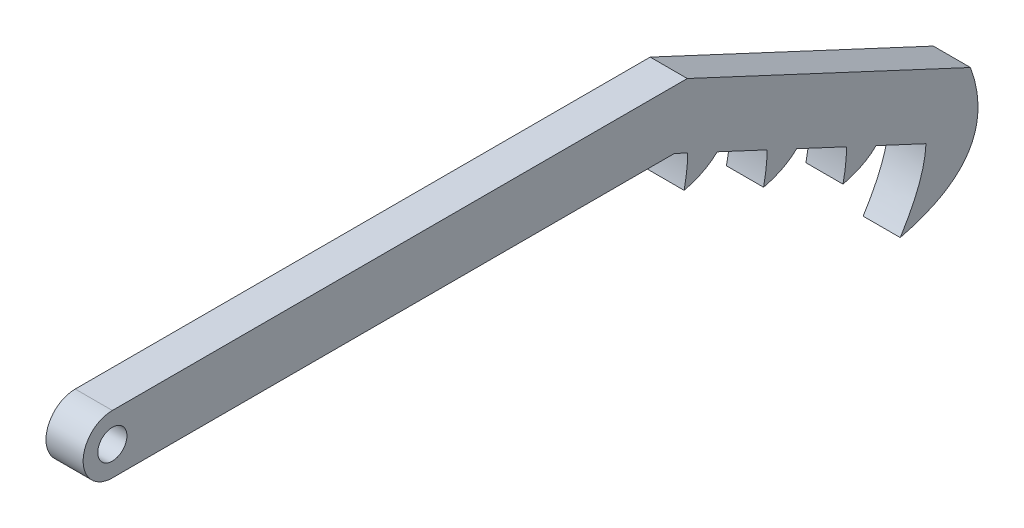
SolidWorks part; units mm, degrees
ref_plane "Front Plane" through (0, 0, 0) normal (0, 0, 1) x (1, 0, 0)
ref_plane "Top Plane" through (0, 0, 0) normal (0, 1, 0) x (1, 0, 0)
ref_plane "Right Plane" through (0, 0, 0) normal (1, 0, 0) x (0, 0, -1)
sketch "Sketch1" plane through (0, 0, 0) normal (1, 0, 0) x (0, 0, -1)
  line L0 (-57.9219, 44.5435) -> (-40.0493, 54.8622)
  line L1 (-40.0493, 49.8622) -> (56.1047, 49.8622)
  line L2 (56.1047, 49.8622) -> (102.5472, 28.2057)
  line L3 (-40.0493, 59.8622) -> (58.3217, 59.8622)
  line L4 (58.3217, 59.8622) -> (106.7734, 37.2688)
  line L5 (56.1047, 49.8622) -> (84.5622, 36.5923) construction
  line L6 (58.3217, 59.8622) -> (88.7883, 45.6554) construction
  line L7 (102.5472, 28.2057) -> (106.7734, 37.2688)
  line L8 (102.5472, 28.2057) -> (111.6103, 23.9795)
  line L9 (93.4842, 32.4319) -> (106.7734, 37.2688)
  circle A0 centre (-57.9219, 44.5435) radius 15.875
  circle A1 centre (-40.0493, 54.8622) radius 4.7625
  circle A2 centre (-40.0493, 54.8622) radius 2.5
  circle A3 centre (-40.0493, 54.8622) radius 5
  parabola Q0 (106.7734, 37.2688) -> (94.7552, 18.0752) focus (102.5472, 28.2057) apex (107.0788, 26.0926)
  parabola Q1 (99.1632, 29.7837) -> (94.7552, 18.0752) focus (93.4842, 32.4319) apex (98.5101, 34.2612)
  parabola Q2 (93.4202, 43.4955) -> (84.9631, 30.8885) focus (87.9414, 37.2725) apex (91.341, 34.5621)
  parabola Q3 (85.5686, 36.123) -> (84.9631, 30.8885) focus (78.3442, 40.2408) apex (83.762, 43.3694)
  parabola Q4 (79.8256, 49.8348) -> (71.3685, 37.2277) focus (74.3468, 43.6117) apex (77.7464, 40.9013)
  parabola Q5 (71.974, 42.4623) -> (71.3685, 37.2277) focus (64.7496, 46.58) apex (70.1674, 49.7086)
  parabola Q6 (66.2309, 56.1741) -> (57.7739, 43.567) focus (60.7522, 49.951) apex (64.1518, 47.2406)
  parabola Q7 (58.3794, 48.8015) -> (57.7739, 43.567) focus (51.155, 52.9193) apex (56.5728, 56.0479)
  point P12 (93.4842, 32.4319)
  point P19 (100.1288, 34.8504)
  point P30 (0, 0)
  dimension "D1" = 10
  dimension "D2" = 12.4745
  dimension "D3" = 5
  dimension "D4" = 15
extrude "Boss-Extrude1" add sketch "Sketch1" along normal blind 6.35 contours A2 A1 | A3 A0 A1 | L0 A3 A0 | A0 A3 L0 | Q6 L4 L3 A3 L1 L2 | L4 Q6 L2 Q4 | L4 Q4 L2 Q2 | L4 Q2 L2 L9 | L9 L2 L7 | Q0 L7 L8 | L2 Q1 Q0 L8 | L2 Q3 Q2 | L2 Q5 Q4 | L2 Q7 Q6 | A2 region at (0, 52.862, 44.5166) region at (0, 51.9936, 44.0152) region at (0, 53.0598, 44.5079) region at (0, 59.3323, 41.2471) region at (0, 54.7102, -15.0994) region at (0, 47.8087, -72.3396) region at (0, 46.1053, -60.0268) region at (0, 41.4694, -85.9342) region at (0, 37.45, -97.3772) region at (0, 39.7661, -73.6214) region at (0, 30.7591, -105.9447) region at (0, 32.6355, -100.9349) region at (0, 33.4268, -87.216) region at (0, 23.9786, -100.9688)
sketch "Sketch2" plane through (6.35, 0, 0) normal (1, 0, 0) x (0, 0, -1)
  arc A0 (-40.0493, 59.8622) -> (-40.0493, 49.8622) centre (-40.0493, 54.8622) ccw construction
  point P0 (-40.0493, 54.8622)
  point P1 (0, 0)
hole_wizard "Ø5.0mm Dowel Hole1" positions "Sketch2" profile "Sketch3" hole size "Ø5.0" standard "ANSI Metric" end condition through all
sketch "Sketch3" plane through (6.35, 54.8622, 40.0493) normal (0, 1, 0) x (0, 0, -1)
  line L0 (0, 0) -> (0, 6.35)
  line L1 (0, 6.35) -> (2.5, 6.35)
  line L2 (2.5, 6.35) -> (2.5, 0)
  line L5 (2.5, 0) -> (0, 0)
  line L11 (0, -6.35) -> (0, 107.95) construction
  dimension "Thru Hole Dia." = 5
  dimension "Thru Hole Depth" = 6.35
